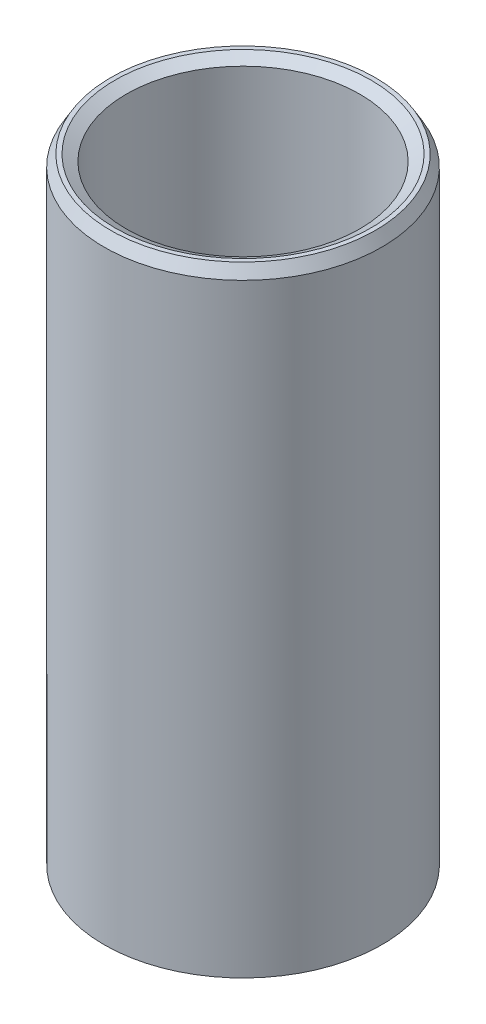
SolidWorks part; units mm, degrees
ref_plane "Front Plane" through (0, 0, 0) normal (0, 0, 1) x (1, 0, 0)
ref_plane "Top Plane" through (0, 0, 0) normal (0, 1, 0) x (1, 0, 0)
ref_plane "Right Plane" through (0, 0, 0) normal (1, 0, 0) x (0, 0, -1)
sketch "Sketch1" plane through (0, 0, 0) normal (0, 1, 0) x (1, 0, 0)
  circle A0 centre (0, 0) radius 47.5
  dimension "SLEEVE_OD" = 95
extrude "Boss-Extrude1" add sketch "Sketch1" along normal blind 212.7412
sketch "Sketch2" plane through (0, 0, 0) normal (0, 1, 0) x (1, 0, 0)
  circle A0 centre (0, 0) radius 39.9475
  dimension "BORE_D" = 79.895
extrude "Cut-Extrude1" cut sketch "Sketch2" along normal through all
chamfer "Chamfer1" distance 3.8493 angle 30 4 edges at (0, 212.7412, 39.9475) (0, 0, 39.9475) (0, 0, 47.5) (0, 212.7412, 47.5) first distance on face at (0, 212.7412, 39.9475) first distance on face at (0, 0, 39.9475) first distance on face at (0, 212.7412, 47.5)
